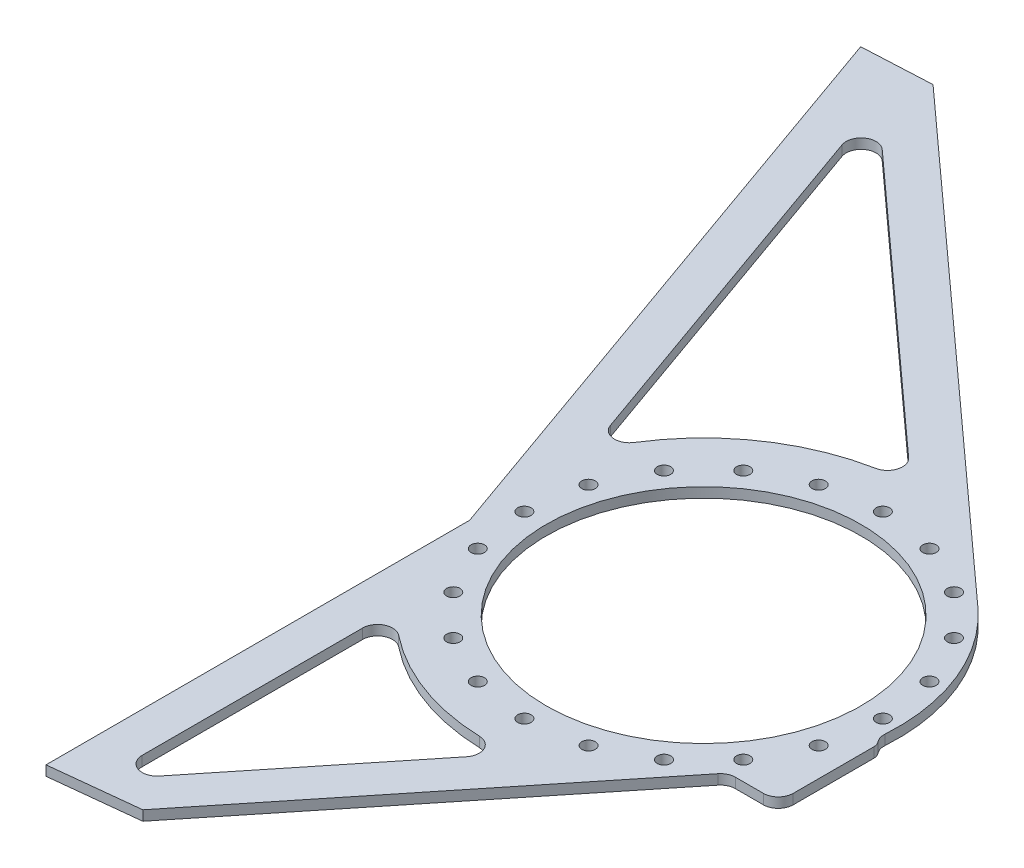
SolidWorks part; units mm, degrees
ref_plane "Plan de face" through (0, 0, 0) normal (0, 0, 1) x (1, 0, 0)
ref_plane "Plan de dessus" through (0, 0, 0) normal (0, 1, 0) x (1, 0, 0)
ref_plane "Plan de droite" through (0, 0, 0) normal (1, 0, 0) x (0, 0, -1)
sketch "Esquisse2" plane through (0, 0, 0) normal (0, 1, 0) x (1, 0, 0)
  line L0 (0, 0) -> (0, 525)
  line L1 (0, 525) -> (-250, 1230.6008)
  line L2 (330.8952, 704.5388) -> (-250, 1230.6008)
  line L3 (351.9775, 437.8205) -> (0, 0)
  line L4 (0, 525) -> (-250, 525) construction
  line L5 (-250, 525) -> (-250, 1230.6008) construction
  line L6 (200, 560) -> (200, 365) construction
  line L9 (200, 560) -> (255.6231, 388.8098) construction
  line L10 (40, 113.596) -> (40, 411.9324)
  line L11 (40, 113.596) -> (224.7547, 343.41)
  line L12 (190.4197, 777.7894) -> (-159.3605, 1094.5523)
  line L13 (-159.3605, 1094.5523) -> (-0.3827, 645.8531)
  line L14 (0, 525) -> (-258, 525) construction
  line L15 (-258, 525) -> (-258, 1253.18) construction
  line L16 (-258, 1253.18) -> (-250, 1230.6008) construction
  circle A0 centre (200, 560) radius 195 construction
  arc A1 (330.8952, 704.5388) -> (351.9775, 437.8205) centre (200, 560) cw
  circle A2 centre (200, 560) radius 180 construction
  circle A3 centre (200, 380) radius 6.75
  circle A4 centre (144.3769, 388.8098) radius 6.75
  circle A5 centre (94.1987, 414.3769) radius 6.75
  circle A6 centre (54.3769, 454.1987) radius 6.75
  circle A7 centre (28.8098, 504.3769) radius 6.75
  circle A8 centre (20, 560) radius 6.75
  circle A9 centre (28.8098, 615.6231) radius 6.75
  circle A10 centre (54.3769, 665.8013) radius 6.75
  circle A11 centre (94.1987, 705.6231) radius 6.75
  circle A12 centre (144.3769, 731.1902) radius 6.75
  circle A13 centre (200, 740) radius 6.75
  circle A14 centre (255.6231, 731.1902) radius 6.75
  circle A15 centre (305.8013, 705.6231) radius 6.75
  circle A16 centre (345.6231, 665.8013) radius 6.75
  circle A17 centre (371.1902, 615.6231) radius 6.75
  circle A18 centre (380, 560) radius 6.75
  circle A19 centre (371.1902, 504.3769) radius 6.75
  circle A20 centre (345.6231, 454.1987) radius 6.75
  circle A21 centre (305.8013, 414.3769) radius 6.75
  circle A22 centre (255.6231, 388.8098) radius 6.75
  circle A23 centre (200, 560) radius 158
  arc A24 (40, 411.9324) -> (224.7547, 343.41) centre (200, 560) ccw
  arc A25 (190.4197, 777.7894) -> (-0.3827, 645.8531) centre (200, 560) ccw
  point P54 (200, 560)
  dimension "D1" = 390
  dimension "D4" = 360
  dimension "D8" = 13.5
  dimension "D10" = 316
  dimension "D13" = 60
  dimension "D15" = 60
  dimension "D2" = 525
  dimension "D3" = 258
  dimension "D5" = 560
  dimension "D6" = 40
  dimension "D7" = 200
  dimension "D11" = 40
  dimension "D12" = 40
  dimension "D14" = 728.18
  dimension "D16" = 40
  dimension "D17" = 250
  dimension "D9" = 20
extrude "Boss.-Extru.1" add sketch "Esquisse2" along normal blind 10
sketch "Esquisse4" plane through (0, 10, 0) normal (0, 1, 0) x (1, 0, 0)
  line L0 (349.6663, 435) -> (400, 435)
  line L1 (400, 435) -> (400, 535)
  line L2 (400, 535) -> (393.3908, 535)
  line L3 (400, 485) -> (200, 485) construction
  line L4 (200, 718) -> (200, 402) construction
  line L6 (393.3908, 535) -> (349.6663, 435)
  arc A0 (351.9775, 437.8205) -> (330.8952, 704.5388) centre (200, 560) ccw construction
  circle A1 centre (200, 560) radius 158 construction
  arc M13 (351.9775, 437.8205) -> (330.8952, 704.5388) centre (200, 560) ccw
  dimension "D1" = 100
  dimension "D2" = 75
  dimension "D3" = 200
extrude "Boss.-Extru.2" add sketch "Esquisse4" against normal up to surface (10 mm away) contours L1 L2 L0 M13 region at (382.9664, 10, -472.2022) up to face at (255.6231, 0, -382.0598)
fillet "Congé1" radius 15 9 edges at (40, 5, -113.596) (224.7547, 5, -343.41) (40, 5, -411.9324) (-0.3827, 5, -645.8531) (190.4197, 5, -777.7894) (-159.3605, 5, -1094.5523) (393.3908, 5, -535) (400, 5, -435) (349.71, 5, -435)
chamfer "Chanfrein1" distance 140 angle 45 2 edges at (0, 5, 0) (-250, 5, -1230.6008) first distance on face at (172.6034, 5, -214.6992) first distance on face at (40.4476, 5, -967.5698)
fillet "Congé2" radius 10 1 edges at (400, 5, -535)
